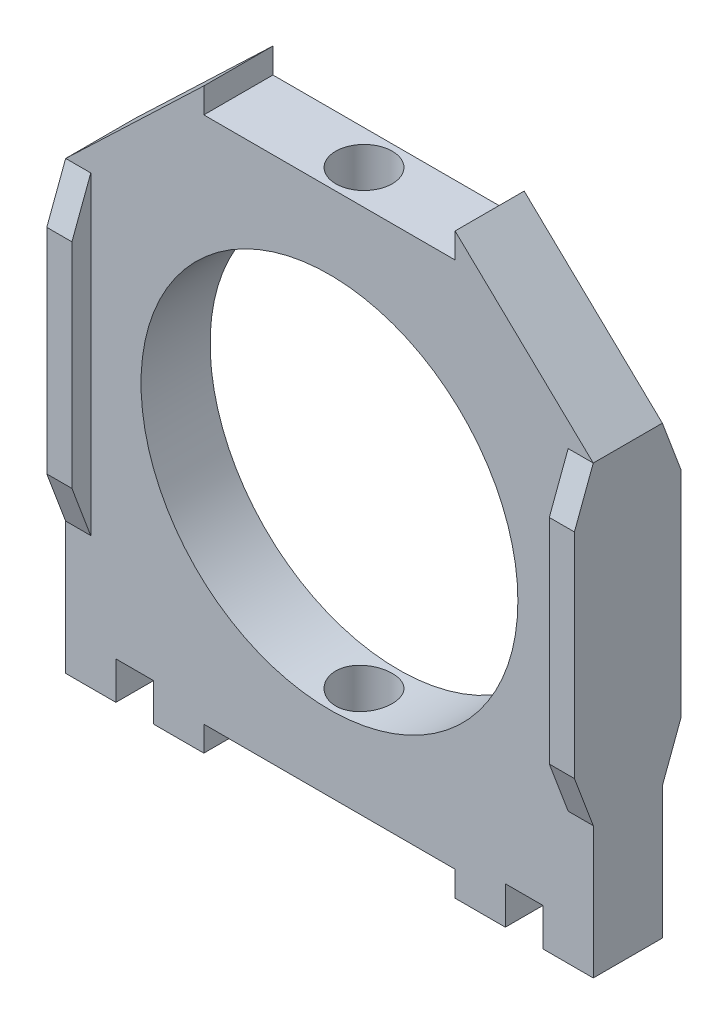
SolidWorks part; units mm, degrees
ref_plane "Front Plane" through (0, 0, 0) normal (0, 0, 1) x (1, 0, 0)
ref_plane "Top Plane" through (0, 0, 0) normal (0, 1, 0) x (1, 0, 0)
ref_plane "Right Plane" through (0, 0, 0) normal (1, 0, 0) x (0, 0, -1)
sketch "Sketch1" plane through (0, 0, 0) normal (0, 0, 1) x (1, 0, 0)
  line L0 (21, 12.5) -> (19, 12.5)
  line L1 (-21, 23) -> (21, 23)
  line L2 (-21, 23) -> (-21, -23)
  line L3 (-21, -23) -> (21, -23)
  line L4 (21, 23) -> (21, -23)
  line L5 (0, -23) -> (0, 23) construction
  line L6 (-21, 0) -> (21, 0) construction
  line L7 (-21, 12.5) -> (-19, 12.5)
  line L8 (-21, 12.5) -> (-21, -12.5)
  line L9 (-21, -12.5) -> (-19, -12.5)
  line L10 (-19, 12.5) -> (-19, -12.5)
  line L11 (21, -12.5) -> (19, -12.5)
  line L12 (19, 12.5) -> (19, -12.5)
  line L13 (-21, 12.5) -> (-10, 23)
  line L14 (21, 12.5) -> (10, 23)
  line L15 (-10, 23) -> (10, 23) construction
  line L16 (10, -23) -> (10, -21)
  line L17 (-10, 23) -> (10, 23)
  line L18 (-10, 23) -> (-10, 21)
  line L19 (-10, 21) -> (10, 21)
  line L20 (10, 23) -> (10, 21)
  line L21 (-10, -23) -> (-10, -21)
  line L22 (-10, -21) -> (10, -21)
  line L23 (14, -23) -> (14, -20)
  line L24 (-17, -23) -> (-14, -23)
  line L25 (-17, -23) -> (-17, -20)
  line L26 (-17, -20) -> (-14, -20)
  line L27 (-14, -23) -> (-14, -20)
  line L28 (17, -20) -> (14, -20)
  line L29 (17, -23) -> (17, -20)
  circle A0 centre (0, 0) radius 15
  point P13 (-19, 0)
  point P22 (0, 23)
  dimension "D1" = 30
  dimension "D2" = 42
  dimension "D3" = 46
  dimension "D4" = 25
  dimension "D5" = 2
  dimension "D6" = 20
  dimension "D7" = 2
  dimension "D8" = 4
  dimension "D9" = 3
  dimension "D10" = 3
extrude "Boss-Extrude1" add sketch "Sketch1" along normal mid plane 5.5 contours L29 L3 L4 L11 L12 L0 L14 L20 L19 L18 L13 L7 L10 L9 L2 L25 L26 L27 L21 L22 L16 L23 L28 A0 region at (20, 13.1229, 0)
extrude "Boss-Extrude2" add sketch "Sketch1<3>" along normal mid plane 8.5 contours L10 L7 L2 L9 | L0 L12 L11 L4 region at (20, 0, 0) region at (-20, 0, 0)
sketch "Sketch1<3>" plane through (0, 0, 0) normal (0, 0, 1) x (1, 0, 0) same geometry as "Sketch1"
sketch "Sketch2" plane through (-21, 0, 0) normal (-1, 0, 0) x (0, 0, 1)
  line L0 (0, 12.5) -> (0, -23) construction
  line L1 (2.75, 12.5) -> (-2.75, 12.5) construction
  line L2 (2.75, -23) -> (-2.75, -23) construction
  line L3 (-4.25, 0) -> (4.25, 0) construction
  line L4 (-4.25, 12.5) -> (-4.25, -12.5) construction
  line L5 (4.25, 12.5) -> (4.25, -12.5) construction
  line L6 (-2.75, 12.5) -> (-4.25, 8.5)
  line L7 (2.75, 12.5) -> (4.25, 8.5)
  line L8 (2.75, -12.5) -> (4.25, -8.5)
  line L9 (-2.75, -12.5) -> (-4.25, -8.5)
  line L17 (-2.75, -12.5) -> (-2.75, -23)
  line L18 (-2.75, -23) -> (2.75, -23)
  line L19 (2.75, -23) -> (2.75, -12.5)
  line L20 (2.75, -12.5) -> (4.25, -12.5)
  line L21 (4.25, -12.5) -> (4.25, 12.5)
  line L22 (4.25, 12.5) -> (2.75, 12.5)
  line L23 (2.75, 12.5) -> (-2.75, 12.5)
  line L24 (-2.75, 12.5) -> (-4.25, 12.5)
  line L25 (-4.25, 12.5) -> (-4.25, -12.5)
  line L26 (-4.25, -12.5) -> (-2.75, -12.5)
  line L27 (-2.75, -12.5) -> (-2.75, -23)
  line L28 (-2.75, -23) -> (2.75, -23)
  line L29 (2.75, -23) -> (2.75, -12.5)
  line L30 (2.75, -12.5) -> (4.25, -12.5)
  line L31 (4.25, -12.5) -> (4.25, 12.5)
  line L32 (4.25, 12.5) -> (2.75, 12.5)
  line L33 (2.75, 12.5) -> (-2.75, 12.5)
  line L34 (-2.75, 12.5) -> (-4.25, 12.5)
  line L35 (-4.25, 12.5) -> (-4.25, -12.5)
  line L36 (-4.25, -12.5) -> (-2.75, -12.5)
  line M18 (2.75, -12.5) -> (4.25, -12.5)
  line M19 (4.25, -12.5) -> (4.25, 12.5)
  line M20 (4.25, 12.5) -> (2.75, 12.5)
  line M22 (-2.75, 12.5) -> (-4.25, 12.5)
  line M23 (-4.25, 12.5) -> (-4.25, -12.5)
  line M24 (-4.25, -12.5) -> (-2.75, -12.5)
  dimension "D1" = 4
  dimension "D2" = 0
extrude "Cut-Extrude1" cut sketch "Sketch2" against normal through all contours L8 M18 M19 | L9 M24 M23 | L6 M22 M23 | L7 M20 M19 region at (-21, 11.1667, -3.75) region at (-21, 11.1667, 3.75) region at (-21, -11.1667, -3.75) region at (-21, -11.1667, 3.75)
hole_wizard "M4 Clearance Hole1" positions "Sketch3" profile "Sketch4" hole size "M4" standard "ISO" end condition through all
sketch "Sketch3" plane through (0, 21, 0) normal (0, 1, 0) x (1, 0, 0)
  point P0 (0, 0)
sketch "Sketch4" plane through (0, 21, 0) normal (1, 0, 0) x (0, 0, 1)
  line L0 (0, 0) -> (0, 44)
  line L1 (0, 44) -> (2.25, 44)
  line L2 (2.25, 44) -> (2.25, 0)
  line L5 (2.25, 0) -> (0, 0)
  line L11 (0, -6.35) -> (0, 107.95) construction
  dimension "Thru Hole Dia." = 4.5
  dimension "Thru Hole Depth" = 44
